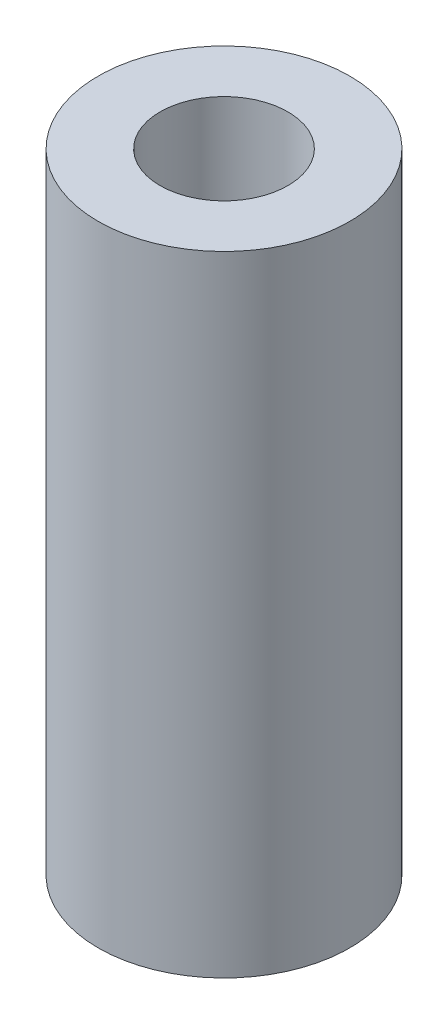
SolidWorks part; units mm, degrees
ref_plane "Front Plane" through (0, 0, 0) normal (0, 0, 1) x (1, 0, 0)
ref_plane "Top Plane" through (0, 0, 0) normal (0, 1, 0) x (1, 0, 0)
ref_plane "Right Plane" through (0, 0, 0) normal (1, 0, 0) x (0, 0, -1)
sketch "Sketch1" plane through (0, 0, 0) normal (0, 1, 0) x (1, 0, 0)
  circle A0 centre (0, 0) radius 6.35
  arc A4 (5.6506, -2.897) -> (-4.0655, 4.8779) centre (0, 0) ccw construction
  circle A5 centre (0, 0) radius 3.2258
  circle A6 centre (0, 0) radius 3.2258
  dimension "D1" = 0.0508
extrude "Boss-Extrude1" add sketch "Sketch1" along normal up to surface (31.75 mm away)
